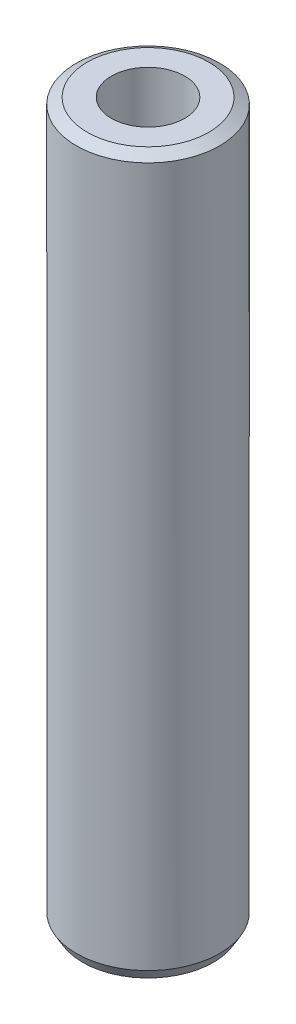
SolidWorks part; units mm, degrees
ref_plane "Front Plane" through (0, 0, 0) normal (0, 0, 1) x (1, 0, 0)
ref_plane "Top Plane" through (0, 0, 0) normal (0, 1, 0) x (1, 0, 0)
ref_plane "Right Plane" through (0, 0, 0) normal (1, 0, 0) x (0, 0, -1)
sketch "Sketch1" plane through (0, 0, 0) normal (0, 1, 0) x (1, 0, 0)
  circle A0 centre (0, 0) radius 60
  dimension "SHAFT_OD" = 120
extrude "Boss-Extrude1" add sketch "Sketch1" along normal blind 600
sketch "Sketch2" plane through (0, 0, 0) normal (0, 1, 0) x (1, 0, 0)
  circle A0 centre (0, 0) radius 30.6929
  dimension "BORE_D" = 61.3859
extrude "Cut-Extrude1" cut sketch "Sketch2" along normal through all
chamfer "Chamfer1" distance 5.2461 angle 60 2 edges at (0, 600, 60) (0, 0, 60) first distance on face at (0, 600, 60) first distance on face at (0, 0, 30.6929)
